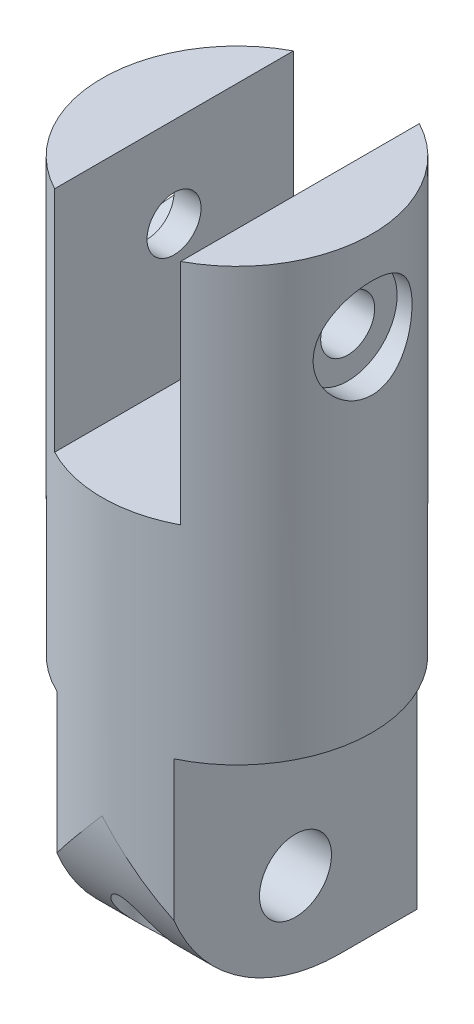
SolidWorks part; units mm, degrees
ref_plane "Front Plane" through (0, 0, 0) normal (0, 0, 1) x (1, 0, 0)
ref_plane "Top Plane" through (0, 0, 0) normal (0, 1, 0) x (1, 0, 0)
ref_plane "Right Plane" through (0, 0, 0) normal (1, 0, 0) x (0, 0, -1)
sketch "Sketch1" plane through (0, 0, 0) normal (0, 0, 1) x (1, 0, 0)
  line L1 (-3.25, 7) -> (3.25, 7)
  line L2 (-3.25, 7) -> (-3.25, -7)
  line L3 (-3.25, -7) -> (3.25, -7)
  line L4 (3.25, 7) -> (3.25, -7)
  line L5 (-3.25, 7) -> (3.25, -7) construction
  line L6 (-3.25, -7) -> (3.25, 7) construction
  point P0 (0, 0)
  dimension "D1" = 6.5
  dimension "D2" = 14
extrude "Boss-Extrude1" add sketch "Sketch1" along normal blind 15
fillet "Fillet1" radius 10 1 edges at (0, -7, 15)
sketch "Sketch2" plane through (3.25, 0, 0) normal (1, 0, 0) x (0, 0, -1)
  line L0 (-7.5, 7) -> (-7.5, -6.6825) construction
  line L1 (-15, 7) -> (0, 7) construction
  arc A0 (-15, 3) -> (-5, -7) centre (-5, 3) ccw construction
  circle A1 centre (-7.5, -2) radius 2
  dimension "D1" = 4
  dimension "D2" = 4.6825
extrude "Cut-Extrude1" cut sketch "Sketch2" against normal through all
sketch "Sketch4" plane through (0, 7, 0) normal (0, 1, 0) x (1, 0, 0)
  line L0 (0, 0) -> (0, -15) construction
  line L1 (3.25, 0) -> (-3.25, 0) construction
  line L2 (3.25, -15) -> (-3.25, -15) construction
  circle A0 centre (0, -7.5) radius 7.5
  dimension "D1" = 15
extrude "Boss-Extrude2" add sketch "Sketch4" along normal blind 24
sketch "Sketch6" plane through (0, 0, 0) normal (0, 0, -1) x (-1, 0, 0)
  line L0 (7.5, 31) -> (-7.5, 31) construction
  line L1 (3.5, 31) -> (-3.5, 31)
  line L2 (3.5, 31) -> (3.5, 18.32)
  line L3 (3.5, 18.32) -> (-3.5, 18.32)
  line L4 (-3.5, 31) -> (-3.5, 18.32)
  point P4 (0, 18.32)
  dimension "D1" = 7
  dimension "D2" = 12.68
extrude "Cut-Extrude2" cut sketch "Sketch6" against normal through all
sketch "Sketch7" plane through (0, 7, 0) normal (0, 1, 0) x (1, 0, 0)
  line L2 (-3.25, -14.2593) -> (-3.25, -15)
  line L3 (-3.25, -15) -> (0, -15)
  line L4 (-3.25, -14.2593) -> (-3.25, -15)
  line L5 (-3.25, -15) -> (0, -15)
  line L6 (0, -15) -> (3.25, -15)
  line L7 (3.25, -15) -> (3.25, -14.2593)
  line L8 (0, -15) -> (3.25, -15)
  line L9 (3.25, -15) -> (3.25, -14.2593)
  line L10 (0, 0) -> (-3.25, 0)
  line L11 (-3.25, 0) -> (-3.25, -0.7407)
  line L12 (0, 0) -> (-3.25, 0)
  line L13 (-3.25, 0) -> (-3.25, -0.7407)
  line L14 (3.25, -0.7407) -> (3.25, 0)
  line L15 (3.25, 0) -> (0, 0)
  line L16 (3.25, -0.7407) -> (3.25, 0)
  line L17 (3.25, 0) -> (0, 0)
  arc A1 (-3.25, -14.2593) -> (0, -15) centre (0, -7.5) ccw
  arc A2 (-3.25, -14.2593) -> (0, -15) centre (0, -7.5) ccw
  arc A3 (0, -15) -> (3.25, -14.2593) centre (0, -7.5) ccw
  arc A4 (0, -15) -> (3.25, -14.2593) centre (0, -7.5) ccw
  arc A5 (0, 0) -> (-3.25, -0.7407) centre (0, -7.5) ccw
  arc A6 (0, 0) -> (-3.25, -0.7407) centre (0, -7.5) ccw
  arc A7 (3.25, -0.7407) -> (0, 0) centre (0, -7.5) ccw
  arc A8 (3.25, -0.7407) -> (0, 0) centre (0, -7.5) ccw
  arc M13 (0, -15) -> (-3.25, -14.2593) centre (0, -7.5) cw
  line M14 (-3.25, -14.2593) -> (-3.25, -15)
  line M15 (-3.25, -15) -> (0, -15)
  dimension "D1" = 0
  dimension "D2" = 0
  dimension "D3" = 0
  dimension "D4" = 0
extrude "Cut-Extrude3" cut sketch "Sketch7" against normal through all contours A6 L12 L13 | A8 L16 L17 | M15 M13 M14 | A4 L8 L9 region at (-2.4457, 7, 14.7798) region at (2.4457, 7, 14.7798) region at (-2.4457, 7, 0.2202) region at (2.4457, 7, 0.2202)
sketch "Sketch8" plane through (-3.5, 0, 0) normal (1, 0, 0) x (0, 0, -1)
  line L0 (-7.5, 18.32) -> (-7.5, 31) construction
  line L1 (-14.1332, 18.32) -> (-0.8668, 18.32) construction
  line L2 (-0.8668, 31) -> (-14.1332, 31) construction
  circle A0 centre (-7.5, 26) radius 1.5
  dimension "D2" = 3
  dimension "D1" = 5
extrude "Cut-Extrude4" cut sketch "Sketch8" against normal mid plane 42
ref_plane "Plane1" through (6.15, 0, 0) normal (-1, 0, 0) x (0, 0, 1)
sketch "Sketch9" plane through (6.15, 0, 0) normal (-1, 0, 0) x (0, 0, 1)
  circle A0 centre (7.5, 26) radius 2.75
  dimension "D1" = 5.5
extrude "Cut-Extrude5" cut sketch "Sketch9" against normal blind 10
ref_plane "Plane2" through (-5, 0, 0) normal (1, 0, 0) x (0, 0, -1)
sketch "Sketch10" plane through (-5, 0, 0) normal (1, 0, 0) x (0, 0, -1)
  line L0 (-7.5, 29.7528) -> (-7.5, 26) construction
  line L1 (-7.5, 29.7528) -> (-10.75, 27.8764)
  line L2 (-10.75, 27.8764) -> (-10.75, 24.1236)
  line L3 (-10.75, 24.1236) -> (-7.5, 22.2472)
  line L4 (-7.5, 22.2472) -> (-4.25, 24.1236)
  line L5 (-4.25, 24.1236) -> (-4.25, 27.8764)
  line L6 (-4.25, 27.8764) -> (-7.5, 29.7528)
  circle A0 centre (-7.5, 26) radius 3.25 construction
  dimension "D1" = 6.5
extrude "Cut-Extrude6" cut sketch "Sketch10" against normal blind 10
sketch "Sketch11" plane through (0, -7, 0) normal (0, -1, 0) x (1, 0, 0)
  line L0 (3.25, 5) -> (-3.25, 5) construction
  circle A1 centre (0, 3) radius 1.25
  circle A3 centre (0, 12.7488) radius 1.25
  dimension "D1" = 2
extrude "Cut-Extrude7" cut sketch "Sketch11" against normal blind 24 contours A3 | A1 region at (0, -7, 3) region at (0, -7, 12.7488)
